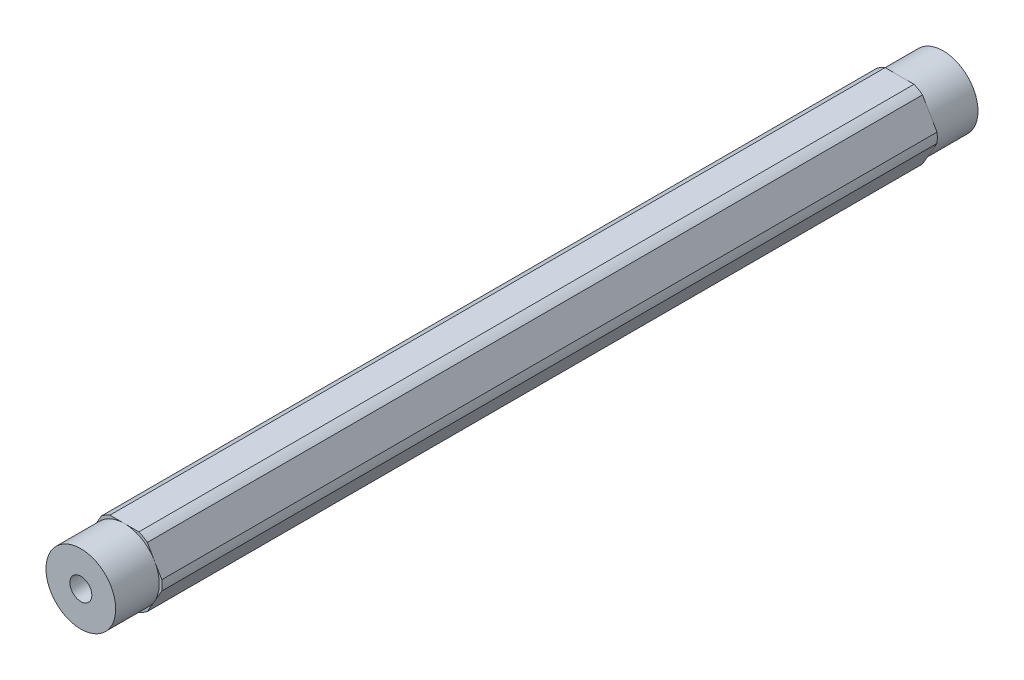
SolidWorks part; units mm, degrees
material "6061-T6 (SS)"
ref_plane "Front Plane" through (0, 0, 0) normal (0, 0, 1) x (1, 0, 0)
ref_plane "Top Plane" through (0, 0, 0) normal (0, 1, 0) x (1, 0, 0)
ref_plane "Right Plane" through (0, 0, 0) normal (1, 0, 0) x (0, 0, -1)
sketch "Sketch1" plane through (0, 0, 0) normal (0, 0, 1) x (1, 0, 0)
  line L1 (3.6662, 6.35) -> (-3.6662, 6.35)
  line L2 (-3.6662, 6.35) -> (-7.3323, 0)
  line L3 (-7.3323, 0) -> (-3.6662, -6.35)
  line L4 (-3.6662, -6.35) -> (3.6662, -6.35)
  line L5 (3.6662, -6.35) -> (7.3323, 0)
  line L6 (7.3323, 0) -> (3.6662, 6.35)
  circle A0 centre (0, 0) radius 6.35 construction
  circle A1 centre (0, 0) radius 2
  circle A2 centre (0, 0) radius 6.875
  point P1 (0, 6.35)
  dimension "D2" = 13.75
  dimension "D3" = 4
  dimension "D1" = 12.7
extrude "Boss-Extrude1" add sketch "Sketch1" along normal mid plane 141.2367 contours L6 A2 L1 L2 L3 L4 L5 A1 region at (3.3439, 5.7918, 0)
sketch "Sketch4" plane through (0, 0, 70.6183) normal (0, 0, 1) x (1, 0, 0)
  circle A0 centre (0, 0) radius 6.35
  circle A1 centre (0, 0) radius 2 construction
  circle A2 centre (0, 0) radius 2
  dimension "D1" = 12.7
extrude "Boss-Extrude2" add sketch "Sketch4" along normal blind 7.9375
mirror "Mirror1" about plane through (0, 0, 0) normal (0, 0, 1) of "Boss-Extrude2"
equation "\"D2@Sketch1\"=13.75mm"
equation "\"D3@Sketch1\"=4mm"
